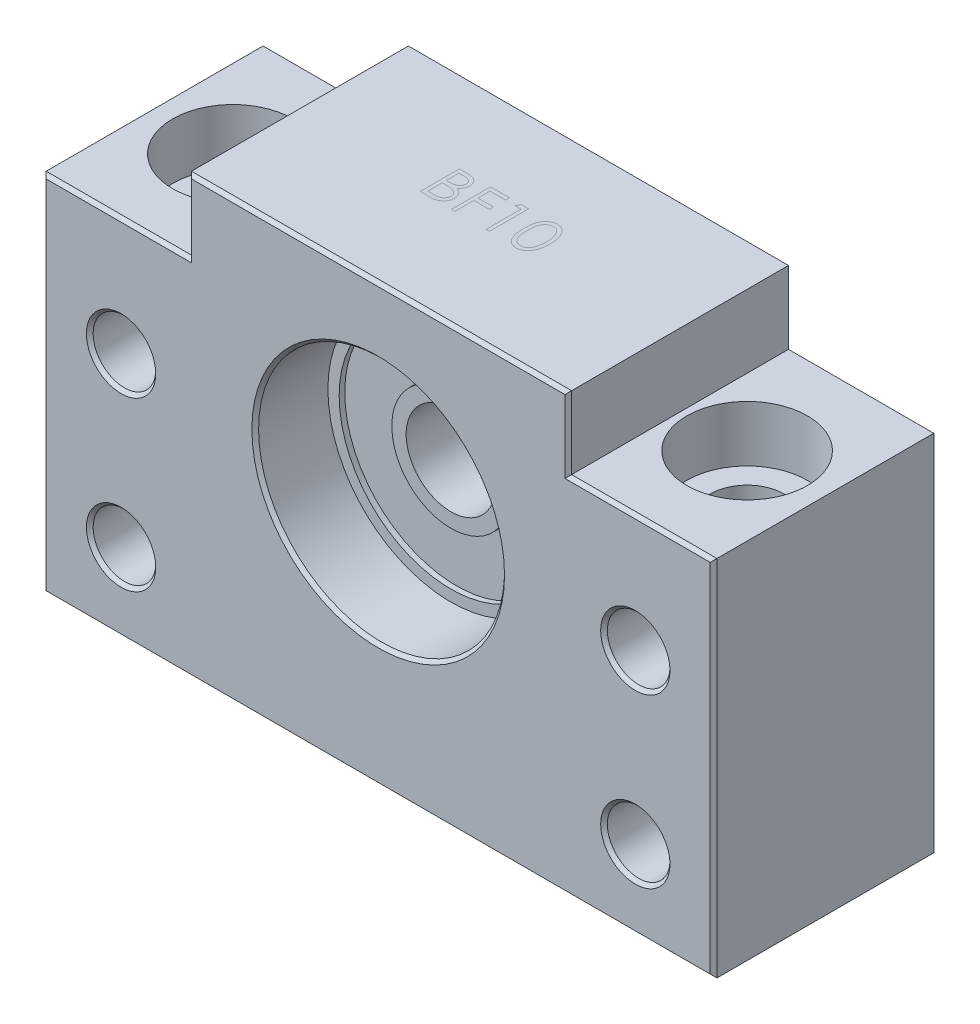
SolidWorks part; units mm, degrees
material "1060 Alloy"
ref_plane "Front Plane" through (0, 0, 0) normal (0, 0, 1) x (1, 0, 0)
ref_plane "Top Plane" through (0, 0, 0) normal (0, 1, 0) x (1, 0, 0)
ref_plane "Right Plane" through (0, 0, 0) normal (1, 0, 0) x (0, 0, -1)
ref_plane "Plane1" through (0, 0, -10) normal (0, 0, -1) x (-1, 0, 0)
sketch "Sketch1" plane through (0, 0, -10) normal (0, 0, -1) x (-1, 0, 0)
  line L0 (30, -0.1215) -> (30, 38.8785) construction
  line L1 (30, 38.8785) -> (-30, 38.8785) construction
  line L2 (-30, 38.8785) -> (-30, -0.1215) construction
  line L3 (-30, -0.1215) -> (30, -0.1215)
  line L4 (30, 32.3785) -> (-30, 32.3785) construction
  line L5 (0, 38.8785) -> (0, 0) construction
  line L6 (-17, 38.8785) -> (-17, 32.3785)
  line L7 (17, 38.8785) -> (17, 32.3785)
  line L8 (30, -0.1215) -> (30, 32.3785)
  line L9 (-30, 32.3785) -> (-30, -0.1215)
  line L10 (-17, 38.8785) -> (17, 38.8785)
  line L11 (30, 32.3785) -> (17, 32.3785)
  line L12 (-30, 32.3785) -> (-17, 32.3785)
  line L13 (17, 38.8785) -> (17, 0) construction
  line L14 (-17, 38.8785) -> (-17, 0) construction
  line L16 (23, 6.8985) -> (-23, 6.8985) construction
  line L17 (23, 6.8985) -> (23, 21.8985) construction
  line L18 (23, 21.8985) -> (-23, 21.8985) construction
  line L19 (-23, 6.8985) -> (-23, 21.8985) construction
  line L20 (23, 6.8985) -> (-23, 21.8985) construction
  line L21 (23, 21.8985) -> (-23, 6.8985) construction
  circle A0 centre (-23, 21.8985) radius 2.8
  circle A1 centre (23, 21.8985) radius 2.8
  circle A2 centre (23, 6.8985) radius 2.8
  circle A3 centre (-23, 6.8985) radius 2.8
  point P4 (-30, 19.3785)
  point P14 (0, 14.3985)
  dimension "D9" = 5.6
  dimension "D10" = 5.6
  dimension "D11" = 5.6
  dimension "D12" = 5.6
  dimension "D1" = 60
  dimension "D2" = 39
  dimension "D3" = 32.5
  dimension "D6" = 15
  dimension "D7" = 22.02
  dimension "D8" = 46
  dimension "D4" = 17
  dimension "D5" = 17
extrude "Boss-Extrude1" add sketch "Sketch1" against normal blind 20
hole_wizard "Ø22.0 (22) Diameter Hole1" positions "Sketch5" profile "Sketch4" hole size "Ø22.0" standard "ANSI Metric"
sketch "Sketch5" plane through (0, 0, -10) normal (0, 0, -1) x (-1, 0, 0)
  line L0 (30, -0.1215) -> (30, 32.3785) construction
  line L1 (-30, -0.1215) -> (30, -0.1215) construction
  point P0 (0, 21.8985)
  dimension "D1" = 30
  dimension "D2" = 22.02
sketch "Sketch4" plane through (0, 21.8985, -10) normal (1, 0, 0) x (0, 1, 0)
  line L0 (0, 0) -> (0, 20)
  line L1 (0, 20) -> (11, 20)
  line L2 (11, 20) -> (11, 0)
  line L5 (11, 0) -> (0, 0)
  line L11 (0, -6.35) -> (0, 107.95) construction
  dimension "Thru Hole Dia." = 22
  dimension "Thru Hole Depth" = 20
sketch "Sketch10" plane through (0, 32.3785, 0) normal (0, 1, 0) x (1, 0, 0)
  line L0 (-30, 0) -> (30, 0) construction
  line L1 (-30, -10) -> (-30, 10) construction
  line L2 (30, -10) -> (30, 10) construction
  line L3 (0, 10) -> (0, -10) construction
  line L4 (-17, 10) -> (17, 10) construction
  line L5 (-17, -10) -> (17, -10) construction
  circle A0 centre (-23, 0) radius 3.3
  circle A1 centre (23, 0) radius 3.3
  dimension "D1" = 6.6
  dimension "D2" = 6.6
  dimension "D3" = 46
  dimension "D4" = 23
extrude "Cut-Extrude3" cut sketch "Sketch10" against normal through all
sketch "Sketch11" plane through (0, 32.3785, 0) normal (0, 1, 0) x (1, 0, 0)
  circle A0 centre (-23, 0) radius 5.4
  circle A1 centre (23, 0) radius 5.4
  dimension "D1" = 10.8
  dimension "D2" = 10.8
extrude "Cut-Extrude4" cut sketch "Sketch11" against normal blind 5
sketch "Sketch12" plane through (0, 0, 0) normal (1, 0, 0) x (0, 0, -1)
  line L13 (0, 0) -> (0, 47.8589) construction
  line L15 (-3.5, 32.8985) -> (3.5, 32.8985)
  line L16 (-10, -0.1215) -> (-10, 47.8589) construction
  line L17 (-12.1904, 21.8985) -> (13.6834, 21.8985) construction
  line L18 (3.5, 25.8985) -> (-3.5, 25.8985) construction
  line L19 (3.5, 25.8985) -> (3.5, 32.8985) construction
  line L25 (-10, -0.1215) -> (10, -0.1215) construction
  line L26 (3.5, 32.8985) -> (-3.5, 32.8985) construction
  line L27 (-3.5, 25.8985) -> (-3.5, 32.8985) construction
  line L28 (3.5, 25.8985) -> (-3.5, 32.8985) construction
  line L29 (3.5, 32.8985) -> (-3.5, 25.8985) construction
  line L30 (3.5, 32.8985) -> (3.5, 31.856)
  line L31 (3.5, 31.856) -> (3, 31.856)
  line L32 (3, 31.856) -> (3, 27.1839)
  line L33 (3, 27.1839) -> (3.5, 27.1839)
  line L34 (3.5, 27.1839) -> (3.5, 25.8985)
  line L35 (3.5, 25.8985) -> (-3.5, 25.8985)
  line L36 (-3.5, 25.8985) -> (-3.5, 27.1839)
  line L37 (-3.5, 27.1839) -> (-3, 27.1839)
  line L38 (-3, 27.1839) -> (-3, 31.8917)
  line L39 (-3, 31.8917) -> (-3.5, 31.8917)
  line L40 (-3.5, 31.8917) -> (-3.5, 32.8985)
  point P0 (0, 29.3985)
  dimension "D1" = 7
  dimension "D2" = 4
  dimension "D3" = 11
  dimension "D4" = 0.5
  dimension "D5" = 0.5
  dimension "D6" = 22.02
revolve "Revolve1" add sketch "Sketch12" angle 360 about L17
chamfer "Chamfer3" distance 0.3 angle 45 26 edges at (0, -0.1215, -10) (30, 16.1285, -10) (23.5, 32.3785, -10) (17, 35.6285, -10) (0, 38.8785, -10) (-17, 35.6285, -10) (-23.5, 32.3785, -10) (-30, 16.1285, -10) (20.2, 21.8985, -10) (-25.8, 21.8985, -10) (-25.8, 6.8985, -10) (20.2, 6.8985, -10) (0, 32.8985, -10) (-23.5, 32.3785, 10) (-17, 35.6285, 10) (0, 38.8785, 10) (17, 35.6285, 10) (23.5, 32.3785, 10) (30, 16.1285, 10) (0, -0.1215, 10) (-30, 16.1285, 10) (20.2, 21.8985, 10) (-25.8, 21.8985, 10) (-25.8, 6.8985, 10) (20.2, 6.8985, 10) (0, 32.8985, 10)
sketch "Sketch13" plane through (0, 38.8785, 0) normal (0, 1, 0) x (1, 0, 0)
  text T0 "BF10"
wrap "Wrap1" sketch "Sketch13" wrap type scribe source sketch "Sketch13" face at (0, 38.8785, 0)
